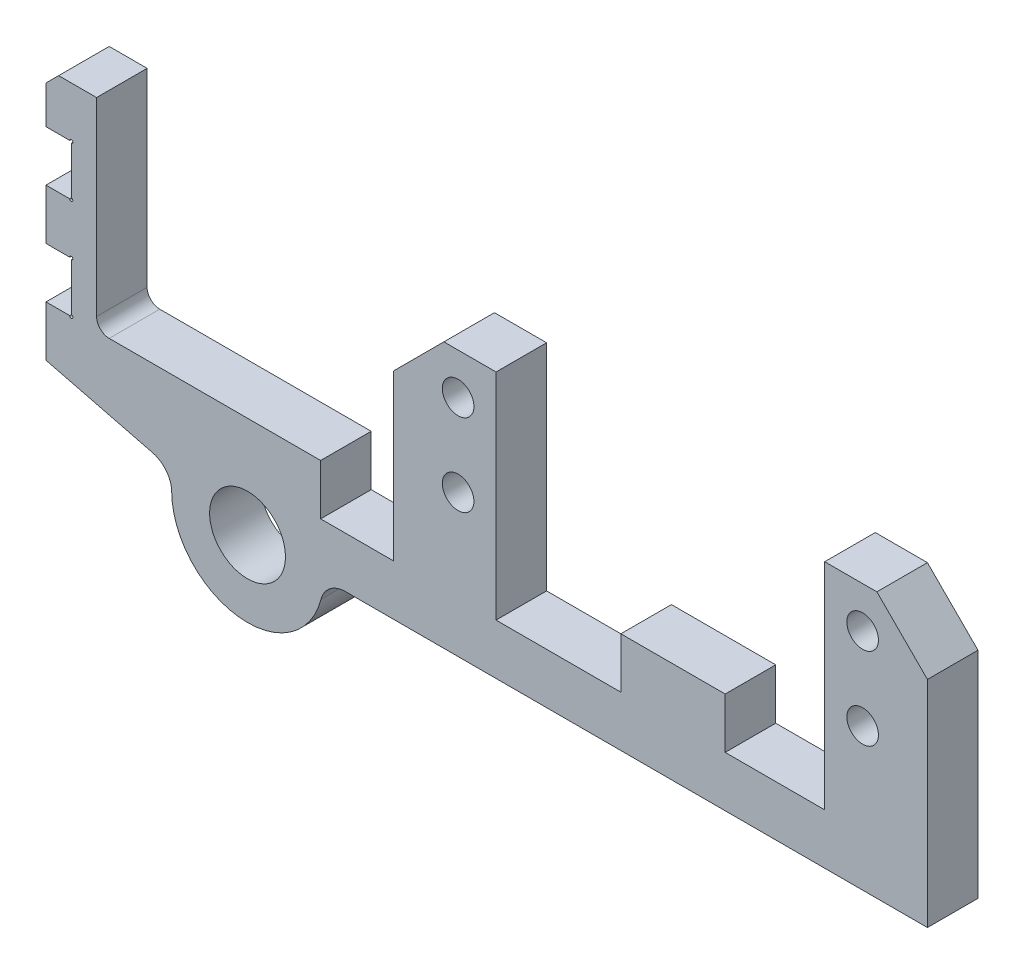
SolidWorks part; units mm, degrees
ref_plane "Front Plane" through (0, 0, 0) normal (0, 0, 1) x (1, 0, 0)
ref_plane "Top Plane" through (0, 0, 0) normal (0, 1, 0) x (1, 0, 0)
ref_plane "Right Plane" through (0, 0, 0) normal (1, 0, 0) x (0, 0, -1)
sketch "Sketch1" plane through (0, 136.6763, 0) normal (0, 1, 0) x (1, 0, 0)
  line L0 (-27.651, -32.4827) -> (-27.651, -60.4545) construction
  line L1 (-103.851, -54.1033) -> (-90.951, -54.1033)
  line L2 (-103.851, -54.1033) -> (-103.851, -60.4533)
  line L3 (-103.851, -60.4533) -> (-90.951, -60.4533)
  line L4 (-90.951, -54.1033) -> (-90.951, -60.4533)
  line L5 (-68.926, -54.1033) -> (-81.826, -54.1033)
  line L6 (-68.926, -54.1033) -> (-68.926, -60.4533)
  line L7 (-68.926, -60.4533) -> (-81.826, -60.4533)
  line L8 (-81.826, -54.1033) -> (-81.826, -60.4533)
  line L9 (-53.251, -54.1033) -> (-40.151, -54.1033)
  line L10 (-53.251, -54.1033) -> (-53.251, -60.4533)
  line L11 (-53.251, -60.4533) -> (-40.151, -60.4533)
  line L12 (-40.151, -54.1033) -> (-40.151, -60.4533)
  line L13 (-27.651, -54.1033) -> (-14.751, -54.1033)
  line L14 (-27.651, -54.1033) -> (-27.651, -60.4533)
  line L15 (-27.651, -60.4533) -> (-14.751, -60.4533)
  line L16 (-14.751, -54.1033) -> (-14.751, -60.4533)
  dimension "D1" = 12.9
  dimension "D2" = 13.1
  dimension "D3" = 12.9
  dimension "D4" = 12.9
  dimension "D5" = 50.6
extrude "Boss-Extrude1" add sketch "Sketch1" against normal blind 6.35
sketch "Sketch2" plane through (0, 130.3263, 0) normal (0, -1, 0) x (-1, 0, 0)
  line L1 (103.851, -60.4533) -> (14.951, -60.4533)
  line L2 (103.851, -60.4533) -> (103.851, -54.1033)
  line L3 (103.851, -54.1033) -> (14.951, -54.1033)
  line L4 (14.951, -60.4533) -> (14.951, -54.1033)
  dimension "D1" = 6.35
  dimension "D2" = 88.9
extrude "Boss-Extrude2" add sketch "Sketch2" along normal blind 12.7
sketch "Sketch3" plane through (0, 136.6763, 0) normal (0, 1, 0) x (1, 0, 0)
  line L1 (-68.926, -54.1033) -> (-81.826, -54.1033)
  line L2 (-68.926, -54.1033) -> (-68.926, -60.4533)
  line L3 (-68.926, -60.4533) -> (-81.826, -60.4533)
  line L4 (-81.826, -54.1033) -> (-81.826, -60.4533)
  line L5 (-14.751, -54.1033) -> (-27.651, -54.1033)
  line L6 (-14.751, -54.1033) -> (-14.751, -60.4533)
  line L7 (-14.751, -60.4533) -> (-27.651, -60.4533)
  line L8 (-27.651, -54.1033) -> (-27.651, -60.4533)
extrude "Boss-Extrude3" add sketch "Sketch3" along normal up to surface (20.6375 mm away)
chamfer "Chamfer1" distance 6.35 angle 45 2 edges at (-14.751, 157.3138, 57.2783) (-81.826, 157.3138, 57.2783)
sketch "Sketch4" plane through (0, 0, 60.4533) normal (0, 0, 1) x (1, 0, 0)
  circle A0 centre (-73.6885, 152.1544) radius 1.9844
  circle A1 centre (-73.6885, 141.8357) radius 1.9844
  circle A2 centre (-22.8885, 141.8357) radius 1.9844
  circle A3 centre (-22.8885, 152.1544) radius 1.9844
extrude "Cut-Extrude1" cut sketch "Sketch4" against normal through all
sketch "Sketch12" plane through (-14.951, 0, 0) normal (1, 0, 0) x (0, 0, -1)
  line L1 (-60.4533, 117.6263) -> (-54.1033, 117.6263)
  line L2 (-60.4533, 117.6263) -> (-60.4533, 130.3263)
  line L3 (-60.4533, 130.3263) -> (-54.1033, 130.3263)
  line L4 (-54.1033, 117.6263) -> (-54.1033, 130.3263)
extrude "Boss-Extrude6" add sketch "Sketch12" along normal up to surface (0.2 mm away) up to face at (-14.751, 140.645, 57.2783)
sketch "Sketch13" plane through (0, 0, 60.4533) normal (0, 0, 1) x (1, 0, 0)
  line L0 (-14.751, 117.6263) -> (-14.751, 150.9638) construction
  line L1 (-103.851, 117.6263) -> (-14.751, 117.6263)
  line L2 (-103.851, 117.6263) -> (-103.851, 123.9763)
  line L3 (-103.851, 123.9763) -> (-14.751, 123.9763)
  line L4 (-14.751, 117.6263) -> (-14.751, 123.9763)
  dimension "D1" = 6.35
extrude "Cut-Extrude2" cut sketch "Sketch13" against normal through all
sketch "Sketch14" plane through (0, 0, 60.4533) normal (0, 0, 1) x (1, 0, 0)
  line L0 (-14.751, 123.9763) -> (-103.851, 123.9763) construction
  line L1 (-119.091, 162.0763) -> (-125.441, 162.0763)
  line L2 (-119.091, 162.0763) -> (-119.091, 136.6763)
  line L3 (-113.2709, 123.9763) -> (-125.441, 123.9763)
  line L4 (-125.441, 162.0763) -> (-125.441, 123.9763)
  line L6 (-103.851, 136.6763) -> (-119.091, 136.6763)
  line L7 (-103.851, 136.6763) -> (-103.851, 123.9763)
  line L8 (-103.851, 123.9763) -> (-113.2709, 123.9763)
  dimension "D1" = 38.1
  dimension "D2" = 6.35
  dimension "D3" = 15.24
extrude "Boss-Extrude7" add sketch "Sketch14" against normal blind 6.35
fillet "Fillet1" radius 1.5875 1 edges at (-119.091, 136.6763, 57.2783)
chamfer "Chamfer2" distance 1.5875 angle 45 1 edges at (-125.441, 162.0763, 57.2783)
sketch "Sketch16" plane through (0, 0, 60.4533) normal (0, 0, 1) x (1, 0, 0)
  line L0 (-125.441, 160.4888) -> (-125.441, 123.9763) construction
  line L1 (-125.441, 155.7263) -> (-122.266, 155.7263)
  line L2 (-125.441, 155.7263) -> (-125.441, 149.3763)
  line L3 (-125.441, 149.3763) -> (-122.266, 149.3763)
  line L4 (-122.266, 155.7263) -> (-122.266, 149.3763)
  line L5 (-119.091, 162.0763) -> (-123.8535, 162.0763) construction
  line L6 (-125.441, 143.0263) -> (-122.266, 143.0263)
  line L7 (-125.441, 143.0263) -> (-125.441, 136.6763)
  line L8 (-125.441, 136.6763) -> (-122.266, 136.6763)
  line L9 (-122.266, 143.0263) -> (-122.266, 136.6763)
  point P10 (-121.4722, 162.0763)
  dimension "D1" = 3.175
  dimension "D2" = 6.35
  dimension "D3" = 3.175
  dimension "D4" = 6.35
  dimension "D5" = 6.35
  dimension "D6" = 6.35
extrude "Cut-Extrude4" cut sketch "Sketch16" against normal blind 6.35
sketch "Sketch17" plane through (0, 0, 60.4533) normal (0, 0, 1) x (1, 0, 0)
  circle A0 centre (-122.266, 155.7263) radius 0.1984
  circle A1 centre (-122.266, 149.3763) radius 0.1984
  circle A2 centre (-122.266, 143.0263) radius 0.1984
  circle A3 centre (-122.266, 136.6763) radius 0.1984
  dimension "D1" = 0.3969
  dimension "D2" = 0.3969
  dimension "D3" = 0.3969
  dimension "D4" = 0.3969
extrude "Cut-Extrude5" cut sketch "Sketch17" against normal blind 6.35
sketch "Sketch18" plane through (0, 0, 60.4533) normal (0, 0, 1) x (1, 0, 0)
  line L0 (-125.441, 123.9763) -> (-125.441, 130.3263)
  line L1 (-125.441, 136.6763) -> (-125.441, 123.9763) construction
  line L2 (-125.441, 130.3263) -> (-100.1326, 123.9763)
  line L3 (-14.751, 123.9763) -> (-125.441, 123.9763) construction
  line L4 (-100.1326, 123.9763) -> (-125.441, 123.9763)
extrude "Cut-Extrude6" cut sketch "Sketch18" against normal blind 6.35
sketch "Sketch19" plane through (0, 0, 60.4533) normal (0, 0, 1) x (1, 0, 0)
  line L0 (-14.751, 123.9763) -> (-100.1326, 123.9763) construction
  circle A0 centre (-100.1326, 123.9763) radius 9.525
  dimension "D1" = 19.05
extrude "Boss-Extrude8" add sketch "Sketch19" against normal blind 6.35
fillet "Fillet2" radius 3.175 2 edges at (-90.6076, 123.9763, 57.2783) (-109.3712, 126.2943, 57.2783)
sketch "Sketch20" plane through (0, 0, 60.4533) normal (0, 0, 1) x (1, 0, 0)
  circle A0 centre (-100.1326, 123.9763) radius 4.7625
extrude "Cut-Extrude7" cut sketch "Sketch20" against normal blind 6.35
